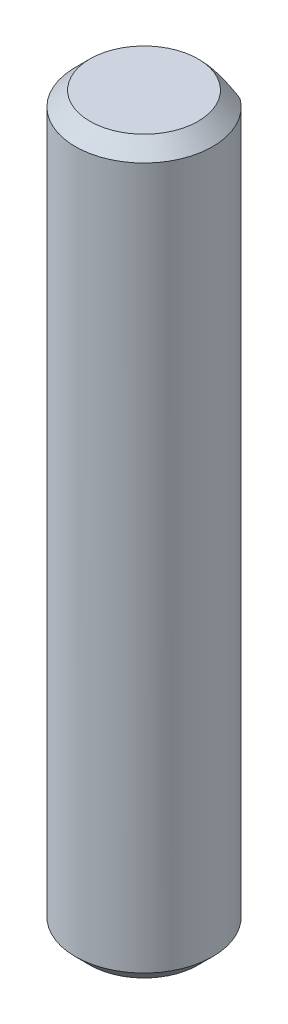
SolidWorks part; units mm, degrees
ref_plane "Front Plane" through (0, 0, 0) normal (0, 0, 1) x (1, 0, 0)
ref_plane "Top Plane" through (0, 0, 0) normal (0, 1, 0) x (1, 0, 0)
ref_plane "Right Plane" through (0, 0, 0) normal (1, 0, 0) x (0, 0, -1)
sketch "Sketch1" plane through (0, 0, 0) normal (0, 0, 1) x (1, 0, 0)
  line L0 (0, -12.5) -> (-1.85, -12.5)
  line L1 (-1.85, -12.5) -> (-2.35, -12)
  line L2 (-2.35, -12) -> (-2.35, 12)
  line L3 (-2.35, 12) -> (-1.85, 12.5)
  line L4 (-1.85, 12.5) -> (0, 12.5)
  line L5 (0, 12.5) -> (0, -12.5)
  dimension "D1" = 135
  dimension "D2" = 135
  dimension "D3" = 0.5
  dimension "D4" = 2.35
  dimension "D5" = 25
revolve "Revolve1" add sketch "Sketch1" angle 360 about L5
sketch "Sketch2" plane through (0, 12.5, 0) normal (0, 1, 0) x (1, 0, 0)
  line L0 (-1.3829, 1.9) -> (1.3829, 1.9)
  line L1 (0, -2.35) -> (0, 1.9) construction
  circle A0 centre (0, 0) radius 2.35 construction
  circle A1 centre (0, 0) radius 2.35
  circle M1 centre (0, 0) radius 1.85
  dimension "D1" = 4.25
extrude "Cut-Extrude1" cut sketch "Sketch2" against normal through all contours L0 A1 M1 region at (0, 12.5, -2.0816)
ref_axis "Axis1" through (0, -12, 0) along (0, 1, 0)
